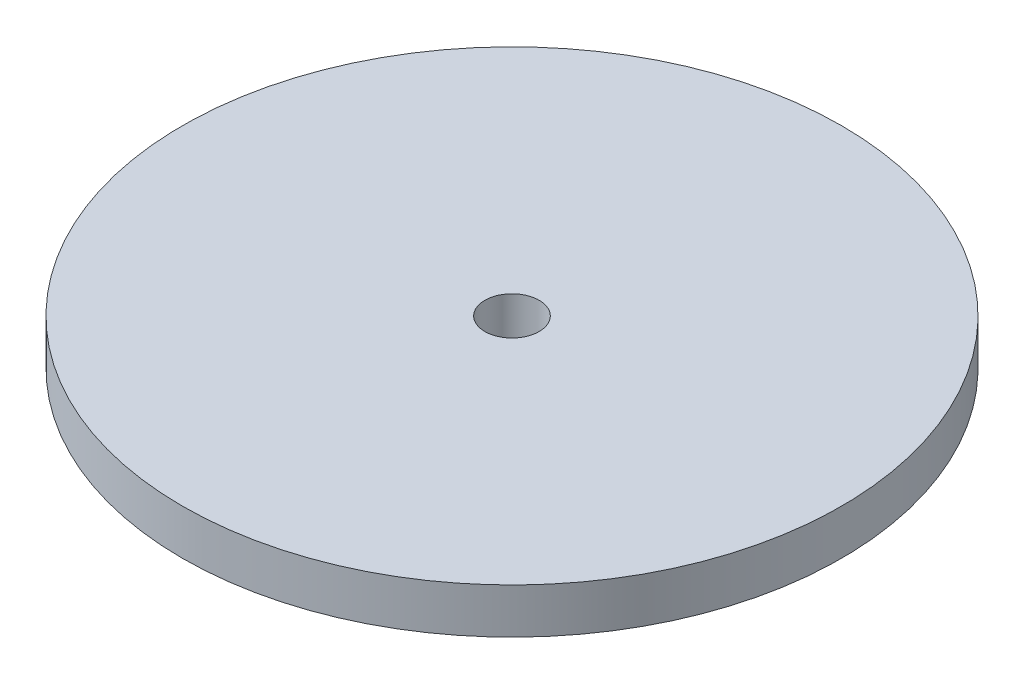
SolidWorks part; units mm, degrees
ref_plane "Front Plane" through (0, 0, 0) normal (0, 0, 1) x (1, 0, 0)
ref_plane "Top Plane" through (0, 0, 0) normal (0, 1, 0) x (1, 0, 0)
ref_plane "Right Plane" through (0, 0, 0) normal (1, 0, 0) x (0, 0, -1)
sketch "Sketch1" plane through (0, 0, 0) normal (0, 1, 0) x (1, 0, 0)
  circle A0 centre (0, 0) radius 36.45
  circle A2 centre (0, 0) radius 3
  dimension "D1" = 72.9
  dimension "D2" = 6
extrude "Boss-Extrude1" add sketch "Sketch1" along normal blind 5
